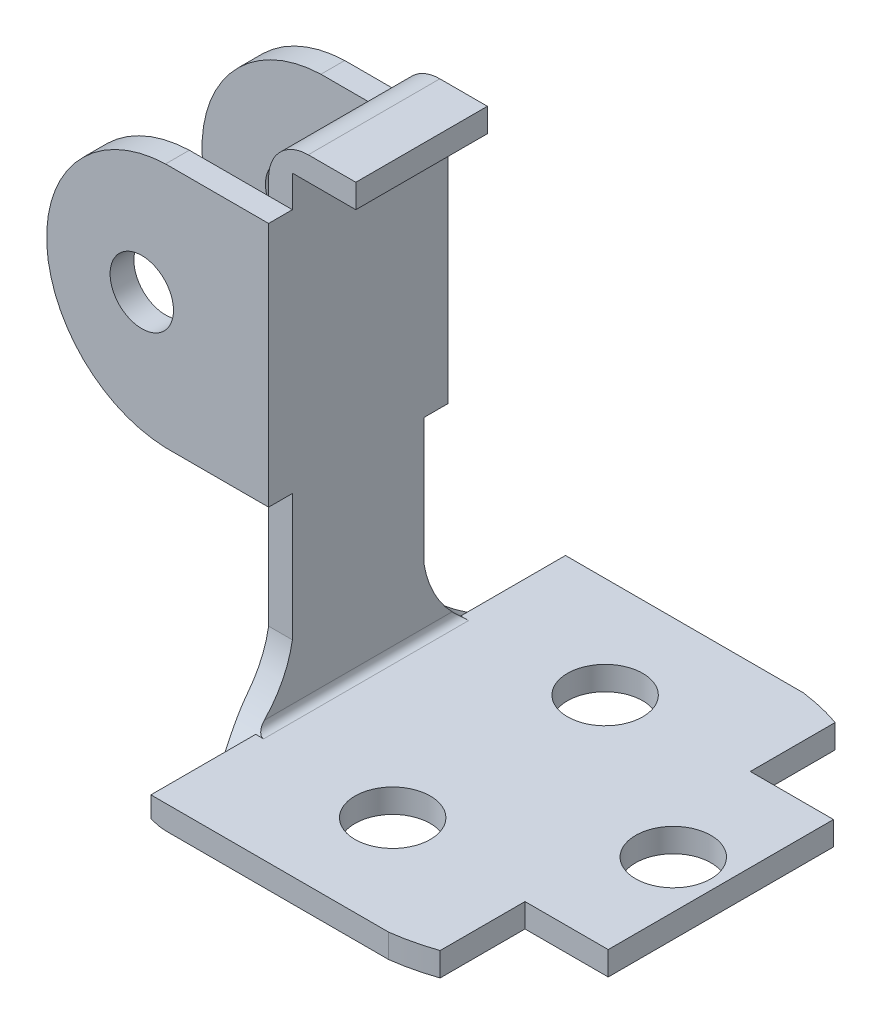
SolidWorks part; units mm, degrees
material "AISI 1020"
ref_plane "Front Plane" through (0, 0, 0) normal (0, 0, 1) x (1, 0, 0)
ref_plane "Top Plane" through (0, 0, 0) normal (0, 1, 0) x (1, 0, 0)
ref_plane "Right Plane" through (0, 0, 0) normal (1, 0, 0) x (0, 0, -1)
sketch "Sketch1" plane through (0, 0, 0) normal (0, 1, 0) x (1, 0, 0)
  line L0 (0, 26.15) -> (30, 26.15)
  line L3 (0, -26.15) -> (30, -26.15)
  line L4 (0, 26.15) -> (0, -26.15)
  line L5 (0, 0) -> (53, 0) construction
  line L6 (17.75, 15.4322) -> (17.75, 11.6834) construction
  line L7 (17.75, -12.5587) -> (17.75, -14.9746) construction
  line L8 (-11.0953, 1.0449) -> (-7.2792, 1.0449) construction
  line L9 (0, 9.3949) -> (-3, 9.3949) construction
  line L11 (0, -7.3051) -> (-3, -7.3051) construction
  line L12 (-3, 9.3949) -> (-3, -7.3051) construction
  arc A2 (30, 26.15) -> (30, -26.15) centre (26.6343, 0) cw
  circle A3 centre (17.75, 13.4) radius 4.75
  circle A5 centre (17.75, -13.4) radius 4.75
  circle A6 centre (39.75, 0) radius 4.75
  point P5 (0, 0)
  point P9 (53, 0)
  dimension "D4" = 9.5
  dimension "D5" = 12.75
  dimension "D1" = 52.3
  dimension "D2" = 53
  dimension "D3" = 30
  dimension "D6" = 13.25
  dimension "D7" = 12.75
  dimension "D8" = 17.75
  dimension "D9" = 16.7
  dimension "D10" = 3
extrude "Boss-Extrude1" add sketch "Sketch1" along normal blind 3
sketch "Sketch3" plane through (0, 0, 0) normal (-1, 0, 0) x (0, 0, 1)
  line L0 (-26.15, 0) -> (26.15, 0) construction
  line L1 (-8.3, 0) -> (8.3, 0)
  line L3 (-8.3, 62) -> (8.3, 62)
  line L5 (8.3, 0) -> (21.3, 0)
  line L6 (8.3, 0) -> (8.3, 11) construction
  line L7 (8.3, 62) -> (8.3, 11)
  line L8 (0, -1.8786) -> (0, 64.4627) construction
  line L9 (-8.3, 62) -> (-8.3, 11)
  line L10 (-8.3, 0) -> (-21.3, 0)
  arc A0 (21.3, 0) -> (8.3, 11) centre (21.3, 13.1818) cw
  arc A1 (-21.3, 0) -> (-8.3, 11) centre (-21.3, 13.1818) ccw
  point P6 (0, 0)
  dimension "D1" = 11
  dimension "D2" = 16.6
  dimension "D3" = 13
extrude "Boss-Extrude3" add sketch "Sketch3" along normal blind 3
sketch "Sketch4" plane through (0, 62, 0) normal (0, 1, 0) x (1, 0, 0)
  line L0 (-3, -8.3) -> (-3, 8.3) construction
  line L1 (-3, -8.3) -> (8, -8.3)
  line L2 (-3, -8.3) -> (-3, 8.3)
  line L3 (-3, 8.3) -> (8, 8.3)
  line L4 (8, -8.3) -> (8, 8.3)
  line L5 (-3, 8.3) -> (0, 8.3) construction
  dimension "D1" = 11
  dimension "D2" = 16.6
extrude "Boss-Extrude4" add sketch "Sketch4" along normal blind 3
sketch "Sketch5" plane through (0, 0, 8.3) normal (0, 0, 1) x (1, 0, 0)
  line L0 (0, 62) -> (0, 58) construction
  line L1 (0, 11) -> (0, 62) construction
  line L2 (0, 58) -> (0, 27)
  line L3 (0, 27) -> (-28, 27) construction
  line L4 (0, 58) -> (-28, 58) construction
  line L5 (-28, 27) -> (-28, 58) construction
  line L6 (0, 27) -> (-13, 27)
  line L7 (0, 58) -> (-13, 58)
  arc A0 (-13, 27) -> (-13, 58) centre (-12.4917, 42.5) cw
  circle A1 centre (-16, 42.5) radius 4
  point P11 (-28, 42.5)
  point P12 (-28, 42.5)
  dimension "D5" = 8
  dimension "D1" = 4
  dimension "D2" = 31
  dimension "D3" = 28
  dimension "D4" = 13
  dimension "D6" = 12
  dimension "D7" = 15.5
extrude "Boss-Extrude5" add sketch "Sketch5" along normal blind 3
mirror "Mirror1" about plane through (0, 0, 0) normal (0, 0, 1) of "Boss-Extrude5"
fillet "Fillet6" radius 5 2 edges at (-3, 65, 0) (-3, 0, 0)
fillet "Fillet7" radius 1 1 edges at (0, 3, 0)
sketch "Sketch7" plane through (0, 3, 0) normal (0, 1, 0) x (1, 0, 0)
  line L0 (39.75, 0) -> (53, 0) construction
  arc A0 (30, -26.15) -> (30, 26.15) centre (26.6343, 0) ccw construction
ref_plane "Plane1" through (0, 3, 0) normal (0, 1, 0) x (1, 0, 0)
sketch "Sketch8" plane through (0, 3, 0) normal (0, 1, 0) x (1, 0, 0)
  line L0 (45.75, 14.2099) -> (45.75, -14.2099)
  line L1 (45.75, -14.2099) -> (35.2548, -14.2099)
  line L2 (35.2548, -14.2099) -> (35.2548, -24.9166)
  line L4 (35.2548, 14.2099) -> (35.2548, 24.9166)
  line L5 (45.75, 14.2099) -> (35.2548, 14.2099)
  arc A0 (30, -26.15) -> (30, 26.15) centre (26.6343, 0) ccw construction
  arc A1 (46.1086, -17.7736) -> (46.1086, 17.7736) centre (26.6343, 0) ccw
  arc A2 (35.2548, -24.9166) -> (46.1086, -17.7736) centre (26.6343, 0) ccw
  circle A3 centre (39.75, 0) radius 4.75 construction
  arc A4 (35.2548, 24.9166) -> (46.1086, 17.7736) centre (26.6343, 0) cw
  dimension "D1" = 6
extrude "Cut-Extrude1" cut sketch "Sketch8" against normal blind 10
